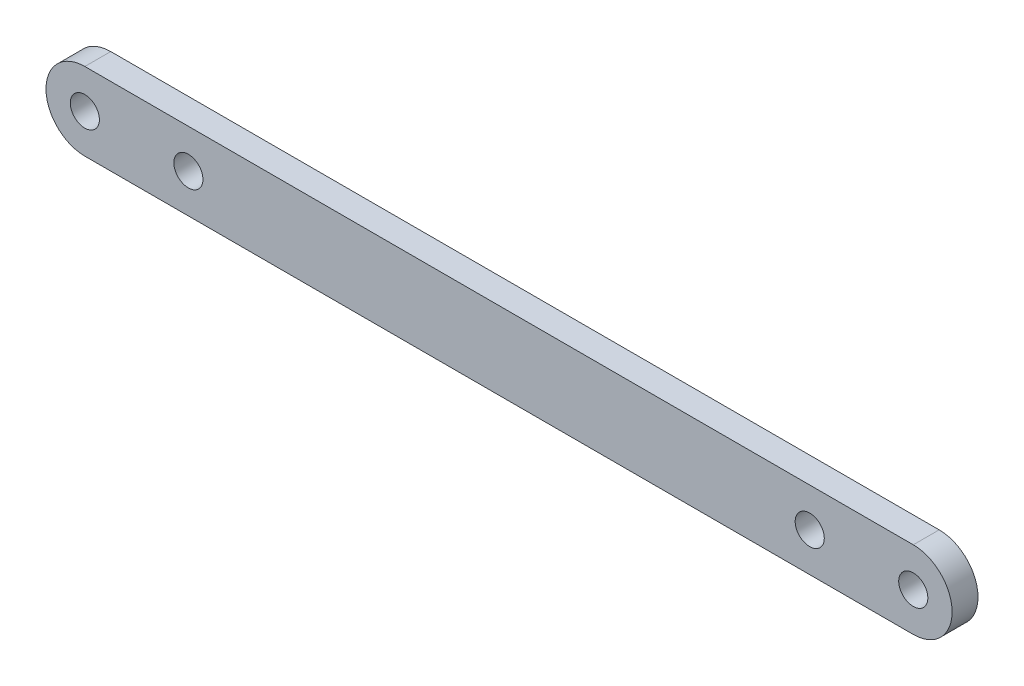
SolidWorks part; units mm, degrees
ref_plane "Front Plane" through (0, 0, 0) normal (0, 0, 1) x (1, 0, 0)
ref_plane "Top Plane" through (0, 0, 0) normal (0, 1, 0) x (1, 0, 0)
ref_plane "Right Plane" through (0, 0, 0) normal (1, 0, 0) x (0, 0, -1)
sketch "Sketch1" plane through (0, 0, 0) normal (0, 0, 1) x (1, 0, 0)
  line L0 (0, 0) -> (-101.6, 0) construction
  line L1 (0, -4.7625) -> (-101.6, -4.7625)
  line L2 (0, 4.7625) -> (-101.6, 4.7625)
  arc A0 (0, -4.7625) -> (0, 4.7625) centre (0, 0) ccw
  arc A1 (-101.6, 4.7625) -> (-101.6, -4.7625) centre (-101.6, 0) ccw
  point P3 (-50.8, 0)
  dimension "D1" = 9.525
  dimension "D2" = 101.6
extrude "Boss-Extrude1" add sketch "Sketch1" along normal blind 3.175
hole_wizard "9/64 (0.14063) Diameter Hole1" positions "Sketch3" profile "Sketch2" hole size "9/64" standard "ANSI Inch" end condition through all
sketch "Sketch3" plane through (0, 0, 3.175) normal (0, 0, 1) x (1, 0, 0)
  point P0 (0, 0)
  point P3 (-101.6, 0)
sketch "Sketch2" plane through (0, 0, 3.175) normal (1, 0, 0) x (0, -1, 0)
  line L0 (0, 0) -> (0, 3.175)
  line L1 (0, 3.175) -> (1.786, 3.175)
  line L2 (1.786, 3.175) -> (1.786, 0)
  line L5 (1.786, 0) -> (0, 0)
  line L11 (0, -6.35) -> (0, 107.95) construction
  dimension "Thru Hole Dia." = 3.572
  dimension "Thru Hole Depth" = 3.175
hole_wizard "9/64 (0.14063) Diameter Hole2" positions "Sketch5" profile "Sketch4" hole size "9/64" standard "ANSI Inch" end condition through all
sketch "Sketch5" plane through (0, 0, 3.175) normal (0, 0, 1) x (1, 0, 0)
  line L0 (-50.8, 4.7625) -> (-50.8, -4.7625) construction
  line L1 (0, 4.7625) -> (-101.6, 4.7625) construction
  line L2 (-101.6, -4.7625) -> (0, -4.7625) construction
  point P0 (-12.7, 0)
  point P13 (-88.9, 0)
  dimension "D1" = 12.7
sketch "Sketch4" plane through (-12.7, 0, 3.175) normal (1, 0, 0) x (0, -1, 0)
  line L0 (0, 0) -> (0, 3.175)
  line L1 (0, 3.175) -> (1.786, 3.175)
  line L2 (1.786, 3.175) -> (1.786, 0)
  line L5 (1.786, 0) -> (0, 0)
  line L11 (0, -6.35) -> (0, 107.95) construction
  dimension "Thru Hole Dia." = 3.572
  dimension "Thru Hole Depth" = 3.175
